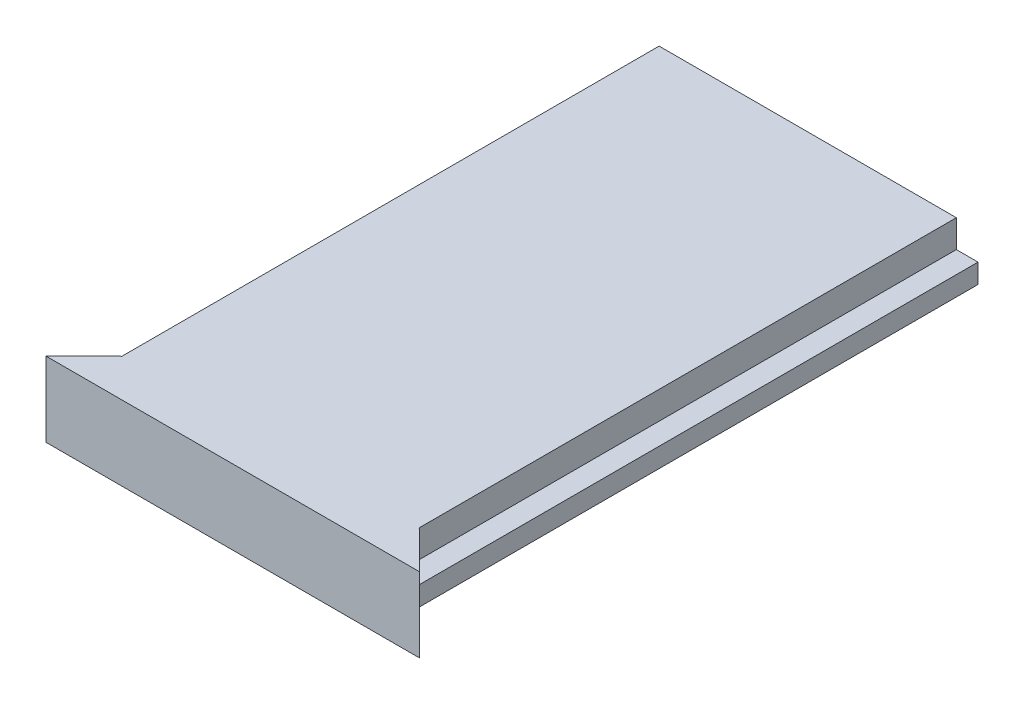
SolidWorks part; units mm, degrees
ref_plane "Front Plane" through (0, 0, 0) normal (0, 0, 1) x (1, 0, 0)
ref_plane "Top Plane" through (0, 0, 0) normal (0, 1, 0) x (1, 0, 0)
ref_plane "Right Plane" through (0, 0, 0) normal (1, 0, 0) x (0, 0, -1)
sketch "Sketch1" plane through (0, 0, 0) normal (0, 0, 1) x (1, 0, 0)
  line L1 (-25, 5) -> (25, 5)
  line L2 (-25, 5) -> (-25, -5)
  line L3 (-25, -5) -> (25, -5)
  line L4 (25, 5) -> (25, -5)
  line L5 (-25, 5) -> (25, -5) construction
  line L6 (-25, -5) -> (25, 5) construction
  point P0 (0, 0)
  dimension "D1" = 10
  dimension "D2" = 50
extrude "Boss-Extrude1" add sketch "Sketch1" along normal blind 5
sketch "Sketch2" plane through (0, 0, 0) normal (0, 1, 0) x (1, 0, 0)
  line L0 (-25, -5) -> (-20, 0)
  line L1 (25, -5) -> (20, 0)
  line L2 (25, -5) -> (-25, -5) construction
  line L3 (-25, -5) -> (-25, 0) construction
  line L4 (-25, -5) -> (-25, 0)
  line L5 (25, 0) -> (-25, 0) construction
  line L6 (25, 0) -> (20, 0)
  line L7 (25, -5) -> (25, 0) construction
  line L8 (25, -5) -> (25, 0)
  line L9 (-20, 0) -> (-25, 0)
  dimension "D1" = 45
  dimension "D2" = 45
extrude "Cut-Extrude1" cut sketch "Sketch2" against normal through all both and the other way through all
sketch "Sketch3" plane through (0, 0, 5) normal (0, 0, 1) x (1, 0, 0)
  line L0 (-25, 0) -> (25, 0) construction
  line L1 (-25, 5) -> (-25, -5) construction
  line L2 (25, -5) -> (25, 5) construction
  line L4 (-22.8, 1.3) -> (22.8, 1.3)
  line L5 (-22.8, 1.3) -> (-22.8, -1.3)
  line L6 (-22.8, -1.3) -> (22.8, -1.3)
  line L7 (22.8, 1.3) -> (22.8, -1.3)
  dimension "D1" = 2.2
  dimension "D2" = 2.2
  dimension "D3" = 2.6
  dimension "D4" = 1.3
extrude "Boss-Extrude2" add sketch "Sketch3" against normal blind 77
sketch "Sketch4" plane through (0, 1.3, 0) normal (0, 1, 0) x (1, 0, 0)
  line L8 (20, 0) -> (-20, 0) construction
  line L9 (-19.9, 0) -> (19.9, 0)
  line L10 (-19.9, 0) -> (-19.9, 72)
  line L11 (-19.9, 72) -> (19.9, 72)
  line L12 (19.9, 0) -> (19.9, 72)
  line L13 (22.8, 72) -> (-22.8, 72) construction
  line L14 (22.8, 72) -> (22.8, -2.8) construction
  line L15 (-22.8, 72) -> (-22.8, -2.8) construction
  dimension "D1" = 2.9
  dimension "D2" = 2.9
extrude "Cut-Extrude2" cut sketch "Sketch4" against normal blind 77
sketch "Sketch6" plane through (0, 0, 0) normal (0, 0, -1) x (-1, 0, 0)
  line L2 (-19.9, -1.3) -> (-19.9, 5)
  line L4 (-18.4, -1.3) -> (-18.4, 3)
  line L5 (-19.9, 5) -> (19.9, 5)
  line L7 (19.9, -1.3) -> (19.9, 5)
  line L9 (18.4, -1.3) -> (18.4, 3)
  line L12 (-18.4, 3) -> (18.4, 3)
  line L14 (18.4, -1.3) -> (19.9, -1.3)
  line L15 (-19.9, -1.3) -> (-18.4, -1.3)
extrude "Boss-Extrude3" add sketch "Sketch6" along normal up to surface (72 mm away) up to face at (21.35, 0, -72)
